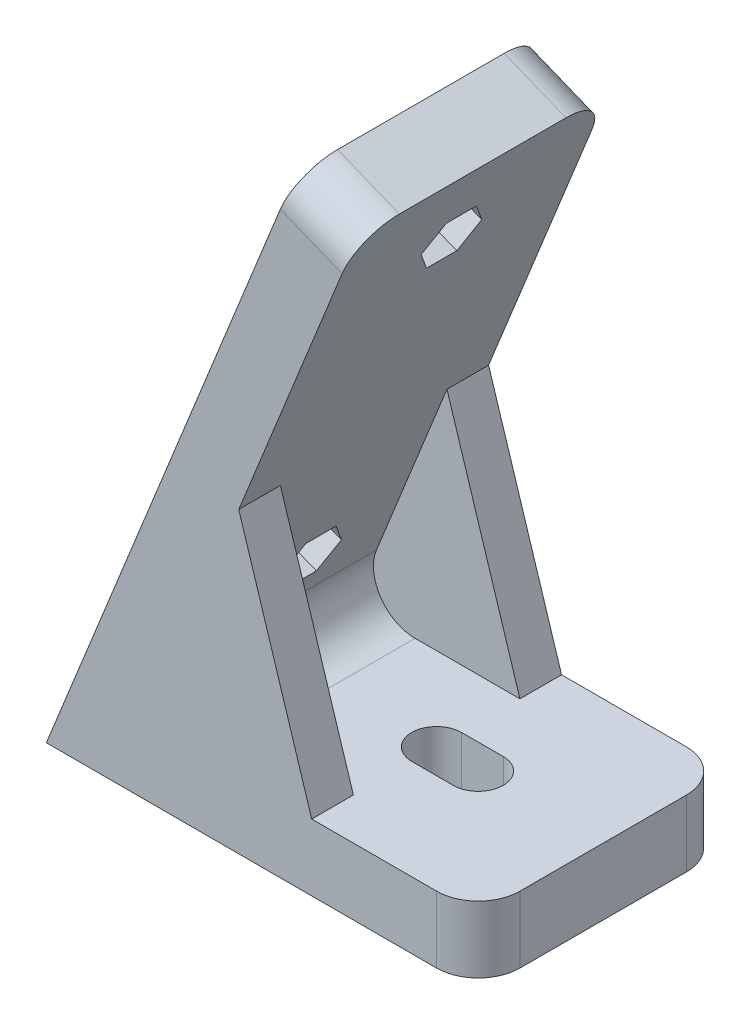
SolidWorks part; units mm, degrees
ref_plane "Front Plane" through (0, 0, 0) normal (0, 0, 1) x (1, 0, 0)
ref_plane "Top Plane" through (0, 0, 0) normal (0, 1, 0) x (1, 0, 0)
ref_plane "Right Plane" through (0, 0, 0) normal (1, 0, 0) x (0, 0, -1)
sketch "Sketch1" plane through (0, 0, 0) normal (0, 0, 1) x (1, 0, 0)
  line L0 (0, 0) -> (29.9685, 74.1747)
  line L4 (11.8605, 8) -> (37.386, 71.1779)
  line L5 (37.386, 71.1779) -> (29.9685, 74.1747)
  line L9 (0, 0) -> (51.8605, 0)
  line L13 (51.8605, 0) -> (51.8605, 8)
  line L15 (11.8605, 8) -> (51.8605, 8)
  dimension "D1" = 68
  dimension "D2" = 8
  dimension "D3" = 8
  dimension "D4" = 80
  dimension "D6" = 40
extrude "Boss-Extrude1" add sketch "Sketch1" along normal mid plane 30
sketch "Sketch2" plane through (0.3799, 8, 0) normal (0, 1, 0) x (1, 0, 0)
  line L0 (36.4805, 0) -> (31.4805, 0) construction
  line L1 (36.4805, -3) -> (31.4805, -3)
  line L2 (36.4805, 3) -> (31.4805, 3)
  line L4 (51.4805, -15) -> (51.4805, 15) construction
  arc A0 (36.4805, -3) -> (36.4805, 3) centre (36.4805, 0) ccw
  arc A1 (31.4805, 3) -> (31.4805, -3) centre (31.4805, 0) ccw
  point P3 (33.9805, 0)
  dimension "D3" = 3
  dimension "D1" = 5
  dimension "D2" = 15
extrude "Cut-Extrude1" cut sketch "Sketch2" against normal through all
sketch "Sketch3" plane through (7.4175, -2.9969, 0) normal (0.9272, -0.3746, 0) x (0, 0, -1)
sketch "Sketch4" plane through (0, 0, 15) normal (0, 0, 1) x (1, 0, 0)
  line L0 (23.0987, 35.8155) -> (31.8605, 8)
  line L3 (11.8605, 8) -> (37.386, 71.1779) construction
  line L5 (51.8605, 8) -> (11.8605, 8) construction
  point P3 (0, 0)
  point P4 (22.9327, 35.4047)
  point P6 (35.1628, 8)
  point P8 (51.8605, 8)
  point P11 (0, 0)
  point P12 (28.9772, 8)
  point P13 (0, 0)
  dimension "D1" = 20
  dimension "D2" = 30
rib "Rib1" sketch "Sketch4" sketch "Sketch4" thickness 5 extrusion direction parallel to sketch draft on no parameters "D1"=5
mirror "Mirror1" about plane through (0, 0, 0) normal (0, 0, 1) of "Rib1"
sketch "Sketch6" plane through (7.4175, -2.9969, 0) normal (0.9272, -0.3746, 0) x (0, 0, -1)
  line L0 (-15, 80) -> (15, 80) construction
  point P0 (0, 70)
  point P2 (0, 25)
  point P9 (0, 80)
  dimension "D1" = 10
  dimension "D2" = 45
hole_wizard "M3 Clearance Hole1" positions "Sketch6" profile "Sketch7" hole size "M3" standard "ANSI Metric" end condition through all
sketch "Sketch7" plane through (33.6399, 61.906, 0) normal (0, 0, 1) x (0.3746, 0.9272, 0)
  line L0 (0, 0) -> (0, 35.7863)
  line L1 (0, 35.7863) -> (1.7, 35.7863)
  line L2 (1.7, 35.7863) -> (1.7, 0.025)
  line L3 (1.7, 0.025) -> (1.725, 0)
  line L5 (1.725, 0) -> (0, 0)
  line L6 (-1.7, 0.025) -> (-1.725, 0) construction
  line L11 (0, -6.35) -> (0, 107.95) construction
  dimension "Thru Hole Dia." = 3.4
  dimension "Thru Hole Depth" = 35.7863
  dimension "Near C'Sink Dia." = 3.45
  dimension "Near C'Sink Angle" = 90
sketch "Sketch8" plane through (7.4175, -2.9969, 0) normal (0.9272, -0.3746, 0) x (0, 0, -1)
  line L1 (3.6373, 70) -> (1.8187, 73.15)
  line L2 (1.8187, 73.15) -> (-1.8187, 73.15)
  line L3 (-1.8187, 73.15) -> (-3.6373, 70)
  line L4 (-3.6373, 70) -> (-1.8187, 66.85)
  line L5 (-1.8187, 66.85) -> (1.8187, 66.85)
  line L6 (1.8187, 66.85) -> (3.6373, 70)
  line L7 (3.6373, 25) -> (1.8187, 28.15)
  line L8 (1.8187, 28.15) -> (-1.8187, 28.15)
  line L9 (-1.8187, 28.15) -> (-3.6373, 25)
  line L10 (-3.6373, 25) -> (-1.8187, 21.85)
  line L11 (-1.8187, 21.85) -> (1.8187, 21.85)
  line L12 (1.8187, 21.85) -> (3.6373, 25)
  circle A0 centre (0, 70) radius 3.15 construction
  circle A1 centre (0, 25) radius 3.15 construction
  dimension "D1" = 6.3
extrude "Cut-Extrude2" cut sketch "Sketch8" against normal blind 3
fillet "Fillet1" radius 5 1 edges at (11.8605, 8, 0)
fillet "Fillet2" radius 5 4 edges at (33.6773, 72.6763, -15) (33.6773, 72.6763, 15) (51.8605, 4, -15) (51.8605, 4, 15)
